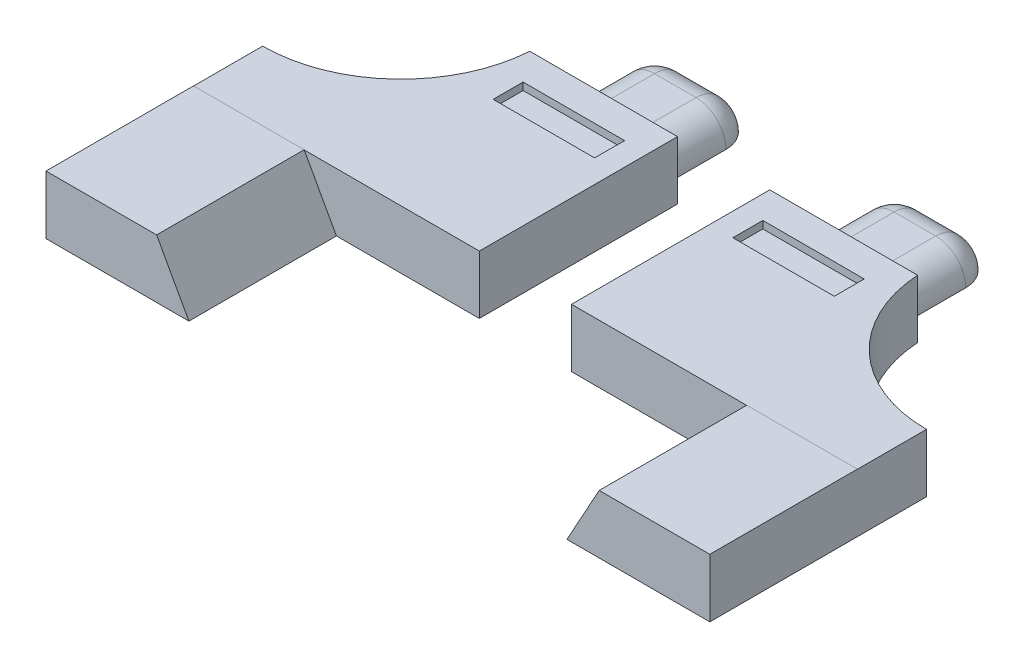
SolidWorks part; units mm, degrees
other "Детальный элемент1"
material "3.3320 (EN-AW 5019)"
ref_plane "Спереди" through (0, 0, 0) normal (0, 0, 1) x (1, 0, 0)
ref_plane "Сверху" through (0, 0, 0) normal (0, 1, 0) x (1, 0, 0)
ref_plane "Справа" through (0, 0, 0) normal (1, 0, 0) x (0, 0, -1)
sketch "Эскиз1" plane through (0, 0, 0) normal (0, 0, 1) x (1, 0, 0)
  line L0 (0, 0) -> (0, 12.7)
  line L1 (0, 12.7) -> (24, 12.7)
  line L2 (24, 12.7) -> (31, 0)
  line L3 (31, 0) -> (0, 0)
  dimension "D1" = 31
  dimension "D2" = 24
  dimension "D3" = 12.7
extrude "Бобышка-Вытянуть1" add sketch "Эскиз1" against normal blind 32
sketch "Эскиз2" plane through (0, 0, -32) normal (0, 0, -1) x (-1, 0, 0)
  line L1 (0, 0) -> (-62, 0)
  line L2 (0, 0) -> (0, 12.6702)
  line L3 (0, 12.6702) -> (-62, 12.6702)
  line L4 (-62, 0) -> (-62, 12.6702)
  dimension "D1" = 62
extrude "Бобышка-Вытянуть2" add sketch "Эскиз2" along normal blind 43
sketch "Эскиз3" plane through (0, 12.6702, 0) normal (0, 1, 0) x (1, 0, 0)
  circle A0 centre (0, 77) radius 30
  point P0 (0, 77)
  point P1 (30, 79.9364)
  point P2 (-6.7792, 47)
  dimension "D1" = 32
  dimension "D2" = 30
  dimension "D3" = 47
  dimension "D4" = 30
extrude "Вырез-Вытянуть1" cut sketch "Эскиз3" against normal through all
sketch "Эскиз4" plane through (0, 0, -75) normal (0, 0, -1) x (-1, 0, 0)
  line L0 (-62, 0) -> (-29.9333, 0) construction
  line L1 (-57, 0) -> (-35, 0)
  line L2 (-57, 0) -> (-57, 6.5)
  line L3 (-57, 6.5) -> (-35, 6.5)
  line L4 (-35, 0) -> (-35, 6.5)
  dimension "D1" = 6.5
  dimension "D2" = 22
  dimension "D3" = 5
extrude "Бобышка-Вытянуть3" add sketch "Эскиз4" along normal blind 22
fillet "Скругление1" radius 6.5 3 edges at (57, 6.5, -86) (35, 6.5, -86) (46, 6.5, -97)
sketch "Эскиз5" plane through (0, 12.6702, 0) normal (0, 1, 0) x (1, 0, 0)
  line L0 (29.9333, 75) -> (62, 75) construction
  line L1 (35, 68.5) -> (57, 68.5)
  line L2 (35, 68.5) -> (35, 62)
  line L3 (35, 62) -> (57, 62)
  line L4 (57, 68.5) -> (57, 62)
  line L5 (62, 75) -> (62, 32) construction
  dimension "D1" = 6.5
  dimension "D2" = 6.5
  dimension "D3" = 5
  dimension "D4" = 22
extrude "Вырез-Вытянуть2" cut sketch "Эскиз5" against normal blind 1.6
ref_plane "Плоскость1" through (72, 0, 0) normal (1, 0, 0) x (0, 0, -1)
mirror "Зеркальное отражение1" about plane through (72, 0, 0) normal (1, 0, 0) of bodies 107
move or copy body "Тело-Переместить/Копировать1" [suppressed] bodies to move or copy 107
